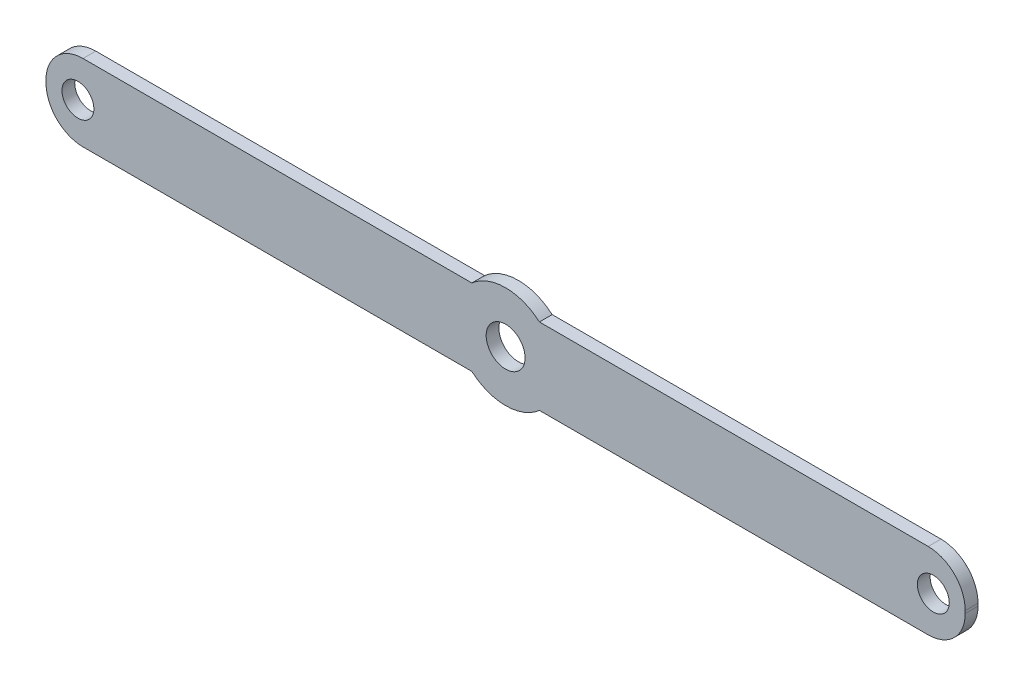
SolidWorks part; units mm, degrees
material "0.6010 (EN-GJL-100)"
ref_plane "Ön Düzlem" through (0, 0, 0) normal (0, 0, 1) x (1, 0, 0)
ref_plane "Üst Düzlem" through (0, 0, 0) normal (0, 1, 0) x (1, 0, 0)
ref_plane "Sağ Düzlem" through (0, 0, 0) normal (1, 0, 0) x (0, 0, -1)
sketch "Çizim1" plane through (0, 0, 0) normal (0, 0, 1) x (1, 0, 0)
  line L0 (29, 0) -> (333.5425, 0)
  line L1 (386.4575, 0) -> (691, 0)
  line L2 (0, -30) -> (1088.2395, -30) construction
  line L3 (29, -60) -> (333.5425, -60)
  line L4 (386.4575, -60) -> (691, -60)
  line L5 (0, -29) -> (0, -31)
  line L6 (720, -29) -> (720, -31)
  line L7 (360, 10) -> (360, -70) construction
  arc A0 (333.5425, 0) -> (386.4575, 0) centre (360, -30) cw
  arc A1 (333.5425, -60) -> (386.4575, -60) centre (360, -30) ccw
  circle A3 centre (360, -30) radius 15.25
  arc A4 (29, -60) -> (0, -31) centre (29, -31) cw
  arc A5 (29, 0) -> (0, -29) centre (29, -29) ccw
  arc A6 (691, -60) -> (720, -31) centre (691, -31) ccw
  arc A7 (691, 0) -> (720, -29) centre (691, -29) cw
  circle A8 centre (695, -30) radius 12.5
  circle A9 centre (25, -30) radius 12.5
  point P18 (0, -60)
  point P21 (0, 0)
  point P24 (720, -60)
  point P27 (720, 0)
  dimension "D3" = 40
  dimension "D4" = 30
  dimension "D6" = 30.5
  dimension "D7" = 29
  dimension "D8" = 25
  dimension "D9" = 25
  dimension "D2" = 25
  dimension "D1" = 720
  dimension "D5" = 30
base flange "Taban-Flanş1" sketch "Çizim1" thickness 10 reverse thickness direction no parameters "D1"=0.7366
sketch "Büküm-Çizgileri1" [suppressed] plane through (0, 0, 0) normal (0, 1, 0) x (1, 0, 0)
sketch "Sınırlandırma-Kutusu1" [suppressed] plane through (0, 0, 0) normal (0, 1, 0) x (1, 0, 0)
sheet metal parameters "Sac-Levha1" thickness 10 parameters "D1"=0.7366
flat pattern "Düz-Çoğaltma1" [suppressed]
sketch "Büküm-Çizgileri2" plane through (0, 0, 0) normal (0, 1, 0) x (1, 0, 0)
sketch3d "Sınırlandırma-Kutusu2" [suppressed]
  line L0 (-358.5063, -50.8547, 0) -> (360.9233, -29.1088, 0) construction
  line L1 (-360.9233, 29.1088, 0) -> (358.5063, 50.8547, 0) construction
  line L2 (-358.5063, -50.8547, 0) -> (-360.9233, 29.1088, 0) construction
  line L3 (360.9233, -29.1088, 0) -> (358.5063, 50.8547, 0) construction
